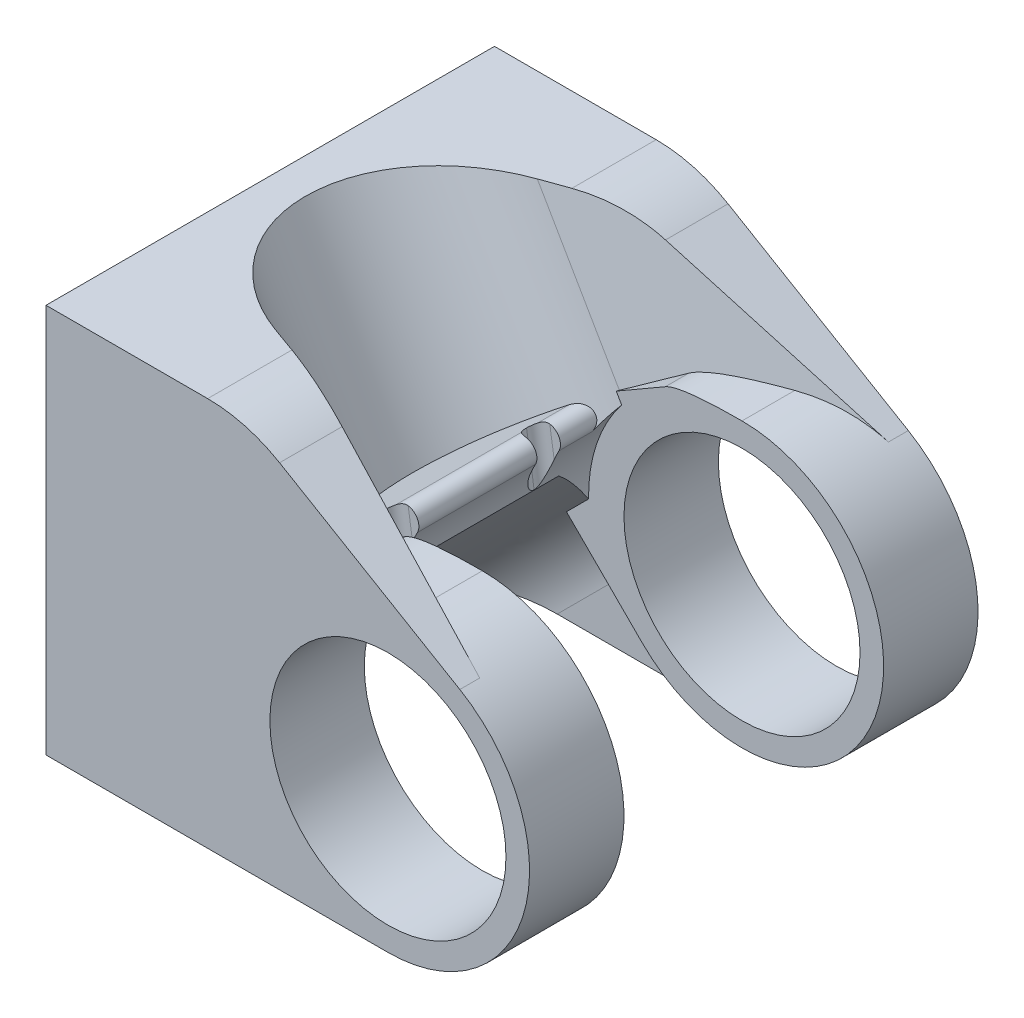
SolidWorks part; units mm, degrees
ref_plane "Спереди" through (0, 0, 0) normal (0, 0, 1) x (1, 0, 0)
ref_plane "Сверху" through (0, 0, 0) normal (0, 1, 0) x (1, 0, 0)
ref_plane "Справа" through (0, 0, 0) normal (1, 0, 0) x (0, 0, -1)
sketch "Эскиз1" plane through (0, 0, 0) normal (0, 0, 1) x (1, 0, 0)
  line L0 (-8.4456, 2.6295) -> (-12.9897, 10.5) construction
  line L1 (-4.2426, 4.2426) -> (-14.4853, -6) construction
  line L2 (-14.4853, -6) -> (0, -6)
  line L3 (0, 0) -> (0, 6) construction
  line L9 (-3.25, 5.6292) -> (-8.4456, 2.6295) construction
  line L11 (0, 6) -> (0, 6.5) construction
  line L14 (-6, 10.5) -> (3.0462, 5.1692)
  line L15 (-14.4853, -6) -> (-14.4853, 10.5)
  line L16 (-14.4853, 10.5) -> (-6, 10.5)
  line L23 (-4.2426, -4.2426) -> (-4.5962, -4.5962) construction
  circle A0 centre (0, 0) radius 5
  circle A1 centre (0, 0) radius 6
  circle A4 centre (0, 0) radius 6.5 construction
  arc A5 (-5.7513, 3.0287) -> (-6.3123, 1.5509) centre (0, 0) ccw
  arc A14 (-6.5025, 3.7513) -> (-5.7513, 3.0287) centre (-6.2313, 3.2815) cw
  arc A16 (-6.3123, 1.5509) -> (-8.9809, -0.4956) centre (0.1088, -9.5852) ccw
sketch "Эскиз2" plane through (0, 0, 0) normal (0, 0, 1) x (1, 0, 0)
  line L0 (3.0462, 5.1692) -> (-6, 10.5)
  line L1 (-6, 10.5) -> (-14.4853, 10.5)
  line L2 (-14.4853, 10.5) -> (-14.4853, -6)
  line L3 (-14.4853, -6) -> (0, -6)
  arc A0 (0, -6) -> (3.0462, 5.1692) centre (0, 0) ccw
extrude "Бобышка-Вытянуть1" add sketch "Эскиз2" along normal mid plane 19
ref_plane "Плоскость1" through (-3.25, 5.6292, 0) normal (-0.5, 0.866, 0) x (0.866, 0.5, 0)
sketch "Эскиз3" plane through (-3.25, 5.6292, 0) normal (-0.5, 0.866, 0) x (0.866, 0.5, 0)
  line L1 (-2.2961, -5.5433) -> (6, -8.9796)
  line L4 (0, 0) -> (-4.2426, 4.2426) construction
  line L5 (-4.2426, 4.2426) -> (0, 6) construction
  line L6 (-2.1213, 5.1213) -> (-2.2961, 5.5433) construction
  line L7 (-2.2961, 5.5433) -> (6, 8.9796)
  line L8 (6, -9.5) -> (6, 9.5) construction
  line L9 (6, 8.9796) -> (6, -8.9796)
  line L10 (6, 0) -> (0, 0) construction
  circle A0 centre (0, 0) radius 6
extrude "Вырез-Вытянуть1" cut sketch "Эскиз3" along normal through all both and the other way through all contours A0 | A0 L1 L9 | A0 L9 L7 region at (0.2308, 7.6388, 6.0152) region at (-3.25, 5.6292, 0) region at (0.2308, 7.6388, -6.0152)
ref_plane "Плоскость2" through (-4.2426, 4.2426, 0) normal (-0.7071, -0.7071, 0) x (-0.7071, 0.7071, 0)
sketch "Эскиз4" plane through (-4.2426, 4.2426, 0) normal (-0.7071, -0.7071, 0) x (-0.7071, 0.7071, 0)
  line L1 (0, -6.5) -> (-12, -6.5)
  line L2 (0, -6.5) -> (0, 6.5)
  line L3 (0, 6.5) -> (-12, 6.5)
  line L4 (-12, -6.5) -> (-12, 6.5)
  line L5 (0, -6.5) -> (-12, 6.5) construction
  line L6 (0, 6.5) -> (-12, -6.5) construction
  line L8 (0, -6.5) -> (0, -2) construction
  line L9 (0, -2) -> (-4, -2) construction
  line L10 (-6, 0) -> (0, 0) construction
  ellipse E0 centre (-4, -2) end of major axis (-4, -6.5) minor radius 4 (0, -2) -> (-4, -6.5) cw
  ellipse E1 centre (-4, 2) end of major axis (-4, 6.5) minor radius 4 (0, 2) -> (-4, 6.5) ccw
  point P0 (-6, 0)
extrude "Вырез-Вытянуть3" cut sketch "Эскиз4" against normal through all both and the other way through all contours L2 E1 L3 L4 L1 E0 region at (0.1881, -0.1881, 0)
sketch "Эскиз5" plane through (0, 0, 0) normal (0, 0, 1) x (1, 0, 0)
  circle A0 centre (0, 0) radius 6.5
extrude "Вырез-Вытянуть4" cut sketch "Эскиз5" against normal mid plane 13
sketch "Эскиз6" plane through (0, 0, 0) normal (0, 0, 1) x (1, 0, 0)
  line L0 (-6.5025, 3.7513) -> (-8.4456, 2.6295)
  line L1 (-8.4456, 2.6295) -> (-8.9809, -0.4956)
  arc A0 (-8.9809, -0.4956) -> (-6.3123, 1.5509) centre (0.1088, -9.5852) cw
  arc A1 (-5.7513, 3.0287) -> (-6.3123, 1.5509) centre (0, 0) ccw construction
  arc A2 (-6.3123, 1.5509) -> (-5.7513, 3.0287) centre (0, 0) cw
  arc A3 (-5.7513, 3.0287) -> (-6.5025, 3.7513) centre (-6.2313, 3.2815) ccw
  arc A4 (-5.7513, 3.0287) -> (-6.5025, 3.7513) centre (-6.2313, 3.2815) ccw construction
extrude "Бобышка-Вытянуть2" add sketch "Эскиз6" along normal mid plane 13
sketch "Эскиз9" plane through (0, 0, 6.5) normal (0, 0, -1) x (-1, 0, 0)
  line L0 (0, 0) -> (0, 6) construction
  line L1 (0, 0) -> (1.5, 2.5981) construction
  line L2 (1.5, 2.5981) -> (3, 5.1962) construction
  line L3 (3, 5.1962) -> (3.25, 5.6292) construction
  line L5 (3.25, 5.6292) -> (10.1378, 1.6525)
  line L6 (4.2426, -4.2426) -> (10.1378, 1.6525)
  line L7 (0, 0) -> (4.2426, -4.2426) construction
  line L8 (0, 6) -> (2.6077, 6) construction
  line L9 (3.25, 5.6292) -> (2.6077, 6) construction
  line L10 (3.25, 5.6292) -> (2.6077, 6) construction
  line L11 (2.6077, 6) -> (0, 6) construction
  circle A0 centre (0, 0) radius 6
  arc A1 (0, 3) -> (1.5, 2.5981) centre (0, 0) cw
  spline S0 degree 2 poles (3.25, 5.6292) (2.6077, 6) (0, 6) knots 0 0 0 1 1 1
  arc M4 (5.7874, -2.959) -> (3.2382, 5.636) centre (0, 0) ccw
  line M12 (3.2382, 5.636) -> (-3.0118, -5.1893)
  arc M13 (-3.0118, -5.1893) -> (0, -6) centre (0, 0) ccw
extrude "Бобышка-Вытянуть3" add sketch "Эскиз9" against normal blind 3 and the other way blind 1 contours A0 M12 | A0 M13 M12 | L6 L5 M4 | S0 A0 M12 | S0 A0 L6 M4 M12 region at (-6.0536, 2.062, 6.5) region at (-7.3524, 1.4681, 6.5) region at (-2.313, 5.6873, 6.5) region at (2.2117, 1.2769, 6.5) region at (-2.1989, -1.2696, 6.5)
mirror "Зеркальное отражение1" about plane through (0, 0, 0) normal (0, 0, 1) of "Бобышка-Вытянуть3"
sketch "Эскиз10" plane through (0, 0, 0) normal (0, 0, 1) x (1, 0, 0)
  circle A0 centre (0, 0) radius 5
extrude "Вырез-Вытянуть5" cut sketch "Эскиз10" against normal through all both and the other way through all
fillet "Скругление1" radius 6 2 edges at (-6, 10.5, 8.0083) (-6, 10.5, -8.0083)
sketch "Эскиз11" plane through (0, 0, 0) normal (0, 1, 0) x (1, 0, 0)
  line L0 (0, 0) -> (0, -3)
  line L1 (0, -3) -> (6, -3)
  point P4 (0, 0)
  point P5 (0, 0)
ref_plane "Плоскость3" through (0, 0, 3) normal (0, 0, 1) x (1, 0, 0)
sketch "Эскиз12" plane through (0, 0, 3) normal (0, 0, 1) x (1, 0, 0)
  line L0 (0, 0) -> (-4.9434, -0.7503)
  line L5 (-4.9434, -0.7503) -> (-6.444, 9.1365)
  line L6 (-6.444, 9.1365) -> (-7.4327, 8.9864)
  line L7 (-7.4327, 8.9864) -> (-5.9321, -0.9004)
  line L8 (-5.9321, -0.9004) -> (-4.9434, -0.7503)
  circle A0 centre (0, 0) radius 5 construction
  spline S0 degree 3 poles (-5.3402, -1.3163) (-5.2761, -1.2205) (-5.2111, -1.1254) (-5.1119, -0.9839) (-5.0786, -0.9369) (-5.0282, -0.8667) (-5.0029, -0.8317) (-4.9711, -0.788) (-4.9562, -0.7677) (-4.9477, -0.7561) (-4.9455, -0.7503) (-4.9434, -0.7503) knots 0 0 0 0 0.000346 0.000346 0.000518 0.000518 0.000605 0.000648 0.00068 0.00068 0.000691 0.000691 0.000691 0.000691 construction
extrude "Вырез-Вытянуть6" cut sketch "Эскиз12" against normal mid plane 1 contours L7 L8 L5 L6 region at (-6.188, 4.118, 3)
fillet "Скругление2" radius 0.5 2 edges at (-6.4672, 2.6253, 2.5) (-6.4672, 2.6253, 3.5)
mirror "Зеркальное отражение2" about plane through (0, 0, 0) normal (0, 0, 1) of "Вырез-Вытянуть6", "Скругление2"
